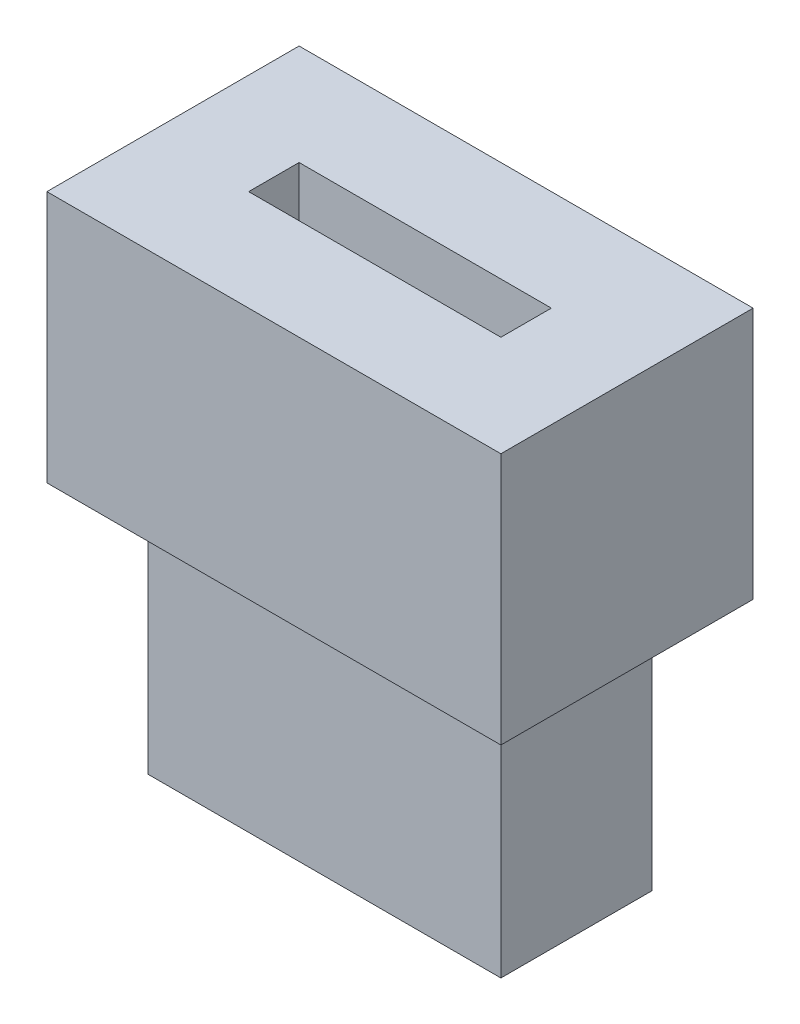
SolidWorks part; units mm, degrees
material "Delrin 2700 NC010, Low Viscosity Acetal Copolymer (SS)"
ref_plane "Front" through (0, 0, 0) normal (0, 0, 1) x (1, 0, 0)
ref_plane "Top" through (0, 0, 0) normal (0, 1, 0) x (1, 0, 0)
ref_plane "Right" through (0, 0, 0) normal (1, 0, 0) x (0, 0, -1)
sketch "Sketch1" plane through (0, 0, 0) normal (0, 1, 0) x (1, 0, 0)
  line L0 (17.5, -7.5) -> (17.5, 7.5)
  line L1 (-22.5, -12.5) -> (22.5, -12.5)
  line L2 (-22.5, -12.5) -> (-22.5, 12.5)
  line L3 (-22.5, 12.5) -> (22.5, 12.5)
  line L4 (22.5, -12.5) -> (22.5, 12.5)
  line L5 (-22.5, -12.5) -> (22.5, 12.5) construction
  line L6 (-22.5, 12.5) -> (22.5, -12.5) construction
  line L7 (-12.5, -2.5) -> (12.5, -2.5)
  line L8 (-12.5, -2.5) -> (-12.5, 2.5)
  line L9 (-12.5, 2.5) -> (12.5, 2.5)
  line L10 (12.5, -2.5) -> (12.5, 2.5)
  line L11 (-12.5, -2.5) -> (12.5, 2.5) construction
  line L12 (-12.5, 2.5) -> (12.5, -2.5) construction
  line L13 (-17.5, 7.5) -> (17.5, 7.5)
  line L14 (-17.5, -7.5) -> (-17.5, 7.5)
  line L15 (-17.5, -7.5) -> (17.5, -7.5)
  point P0 (0, 0)
  point P6 (0, 0)
  point P15 (12.5, 3.4159)
  dimension "D1" = 45
  dimension "D2" = 10
  dimension "D3" = 5
  dimension "D4" = 25
  dimension "D5" = 10
extrude "Boss-Extrude1" add sketch "Sketch1" along normal blind 25 contours L14 L15 L0 L13 L10 L7 L8 L9 | L1 L4 L3 L2 L15 L14 L13 L0 region at (0, 0, 7.1192) region at (-21.9852, 0, 0)
extrude "Boss-Extrude2" add sketch "Sketch1<3>" against normal blind 25 contours L14 L15 L0 L13 L10 L7 L8 L9 region at (0, 0, 7.1192)
sketch "Sketch1<3>" plane through (0, 0, 0) normal (0, 1, 0) x (1, 0, 0) same geometry as "Sketch1"
